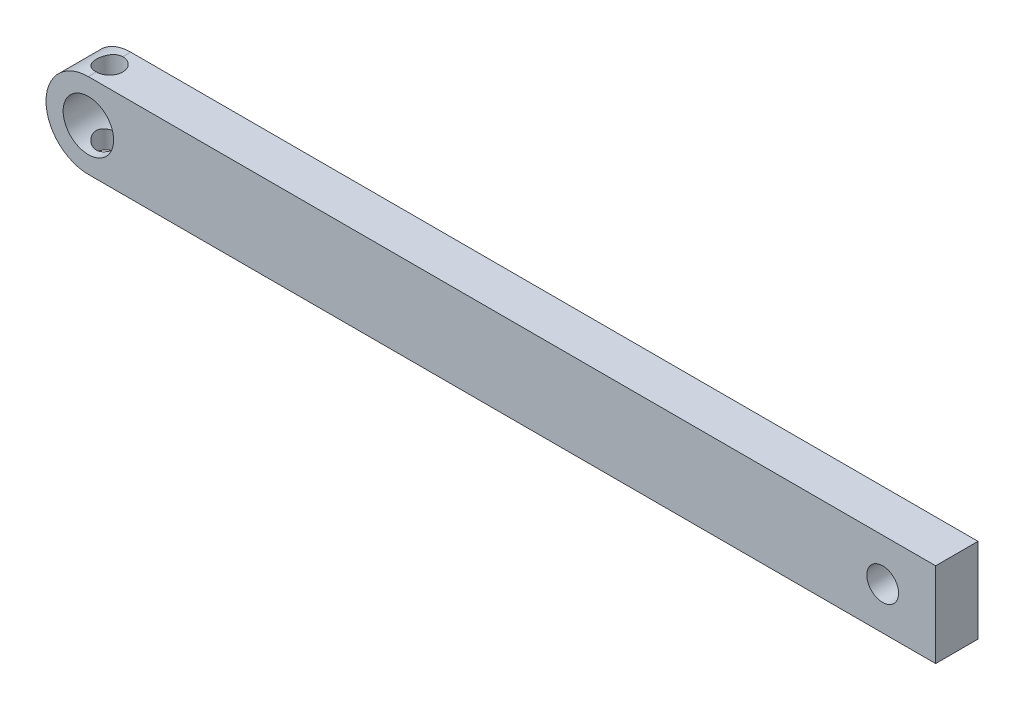
SolidWorks part; units mm, degrees
material "Plain Carbon Steel"
ref_plane "Front Plane" through (0, 0, 0) normal (0, 0, 1) x (1, 0, 0)
ref_plane "Top Plane" through (0, 0, 0) normal (0, 1, 0) x (1, 0, 0)
ref_plane "Right Plane" through (0, 0, 0) normal (1, 0, 0) x (0, 0, -1)
sketch "Sketch1" plane through (0, 0, 0) normal (0, 0, 1) x (1, 0, 0)
  line L0 (0, -8) -> (160, -8)
  line L1 (160, -8) -> (160, 8)
  line L2 (160, 8) -> (0, 8)
  arc A0 (0, 8) -> (0, -8) centre (0, 0) ccw
  dimension "D2" = 8
  dimension "D1" = 160
extrude "Boss-Extrude1" add sketch "Sketch1" along normal blind 8
sketch "Sketch2" plane through (0, 0, 0) normal (0, 0, 1) x (1, 0, 0)
  circle A0 centre (0, 0) radius 4.7625
  circle A1 centre (150, 0) radius 3
  dimension "D1" = 9.525
  dimension "D3" = 6
  dimension "D2" = 150
extrude "Cut-Extrude1" cut sketch "Sketch2" against normal mid plane 40
sketch "Sketch3" plane through (0, 0, 0) normal (0, 0, 1) x (1, 0, 0)
  circle A0 centre (30, 0) radius 4
  dimension "D2" = 8
  dimension "D1" = 30
extrude "Cut-Extrude2" cut sketch "Sketch3" against normal mid plane 1
sketch "Sketch4" plane through (0, 0, 0) normal (0, 1, 0) x (1, 0, 0)
  line L0 (0, -8) -> (0, 0) construction
  circle A0 centre (0, -4) radius 2.5
  dimension "D2" = 5
  dimension "D1" = 4
extrude "Cut-Extrude3" cut sketch "Sketch4" against normal mid plane 40
